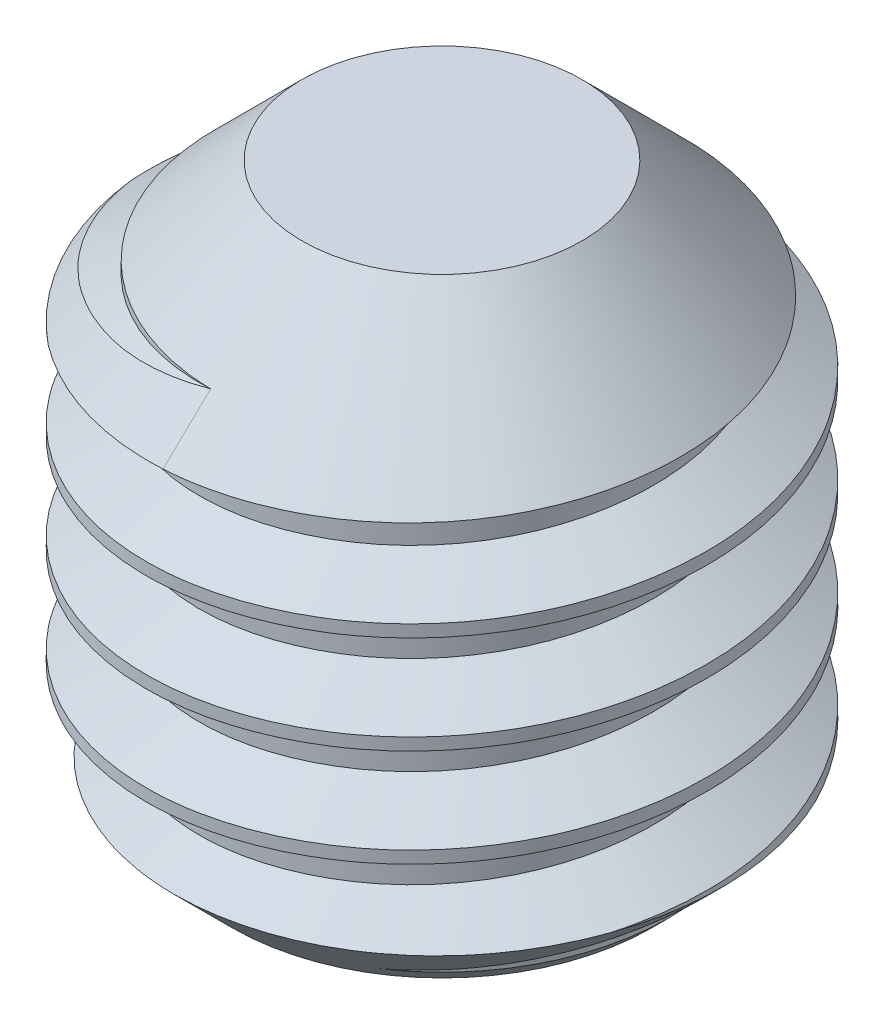
SolidWorks part; units mm, degrees
ref_plane "Plan de face" through (0, 0, 0) normal (0, 0, 1) x (1, 0, 0)
ref_plane "Plan de dessus" through (0, 0, 0) normal (0, 1, 0) x (1, 0, 0)
ref_plane "Plan de droite" through (0, 0, 0) normal (1, 0, 0) x (0, 0, -1)
sketch "Esquisse1" plane through (0, 0, 0) normal (0, 0, 1) x (1, 0, 0)
  line L0 (0, 2.2236) -> (0, -1.7764)
  line L1 (0, -1.7764) -> (-2, -1.7764)
  line L2 (-2, -1.7764) -> (-2, 2.2236)
  line L3 (-2, 2.2236) -> (0, 2.2236)
  dimension "D1" = 4
  dimension "D2" = 2
revolve "Révolution1" add sketch "Esquisse1" angle 360 about L0
thread "Filetage1" pitch 0.7 method cut profile "Profil de filetage2" start angle 0, offset 1, length 0, pitch 0.7, diameter 4
ref_plane "Plan2" through (-2, 3.2236, 0) normal (0, 0, 1) x (-1, 0, 0)
sketch "Profil de filetage2" plane through (-2, 3.2236, 0) normal (0, 0, 1) x (-1, 0, 0)
  line L0 (0, 0) -> (0, 0.7) construction
  line L11 (0, 0) -> (0, 0.6125)
  line L12 (0, 0.6125) -> (-0.3789, 0.3937)
  line L13 (-0.3789, 0.3937) -> (-0.3789, 0.2187)
  line L15 (-0.3789, 0.2187) -> (0, 0)
  line L17 (-0.3789, 0.3062) -> (0, 0.3062) construction
  point P2 (0, 0)
  dimension "Pitch" = 0.7
  dimension "Profile_Angle" = 60
  dimension "Profile_Land" = 0.175
  dimension "Profile_Height" = 0.3789
sketch "Esquisse10" plane through (0, 0, 0) normal (0, 0, 1) x (1, 0, 0)
  line L0 (-1, 2.2236) -> (-2, 1.2236)
  line L1 (1.8828, 2.2236) -> (-1.0916, 2.2236) construction
  line L2 (-2, 1.2236) -> (-2, 2.2236)
  line L3 (-2, 2.2236) -> (-1, 2.2236)
  line L4 (0, 2.2236) -> (0, -1.7764) construction
  line L5 (-0.7816, -1.7764) -> (1.4182, -1.7764) construction
  dimension "D1" = 45
  dimension "D2" = 1
revolve "Enlèvement de matière-Révolution1" cut sketch "Esquisse10" angle 360 about L4
sketch "Esquisse11" plane through (0, -1.7764, 0) normal (0, -1, 0) x (1, 0, 0)
  line L1 (-1.1547, 0) -> (-0.5774, -1)
  line L2 (-0.5774, -1) -> (0.5774, -1)
  line L3 (0.5774, -1) -> (1.1547, 0)
  line L4 (1.1547, 0) -> (0.5774, 1)
  line L5 (0.5774, 1) -> (-0.5774, 1)
  line L6 (-0.5774, 1) -> (-1.1547, 0)
  circle A0 centre (0, 0) radius 1 construction
  point P1 (0.866, 0.5)
  dimension "D1" = 2
extrude "Enlèv. mat.-Extru.1" cut sketch "Esquisse11" against normal blind 1.5
sketch "Esquisse12" plane through (0, 0, 0) normal (0, 0, 1) x (1, 0, 0)
  line L0 (-1.5, -1.7764) -> (1.5, -1.7764)
  line L1 (-1.8356, -1.7764) -> (-0.7816, -1.7764) construction
  line L2 (0.2143, -1.7764) -> (1.7279, -1.7764) construction
  line L3 (0, 0) -> (0, -1.7764) construction
  arc A0 (-1.5, -1.7764) -> (1.5, -1.7764) centre (0, -3.7764) cw
  point P11 (0, -1.7764)
  point P14 (0, -1.2764)
  dimension "D1" = 0.5
  dimension "D2" = 3
revolve "Enlèvement de matière-Révolution2" cut sketch "Esquisse12" angle 360 about L3 region at (-0.5708, -1.5746, 0)
ref_axis "Axe1" through (0, 2.4357, 0) along (0, -1, 0)
sketch "Esquisse13" plane through (0, 0, 0) normal (0, 0, 1) x (1, 0, 0)
  line L0 (0, 2.4357) -> (0, -2.2303) construction
  line L1 (-0.7816, -1.7764) -> (1.4182, -1.7764) construction
  line L2 (1.5, -1.7764) -> (2, -1.2764)
  line L3 (2, -1.2764) -> (2, -1.7764)
  line L4 (2, -1.7764) -> (1.5, -1.7764)
  dimension "D1" = 45
  dimension "D2" = 1.5
revolve "Enlèvement de matière-Révolution3" cut sketch "Esquisse13" angle 360 about axis through (0, 2.4357, 0) along (0, -1, 0)
